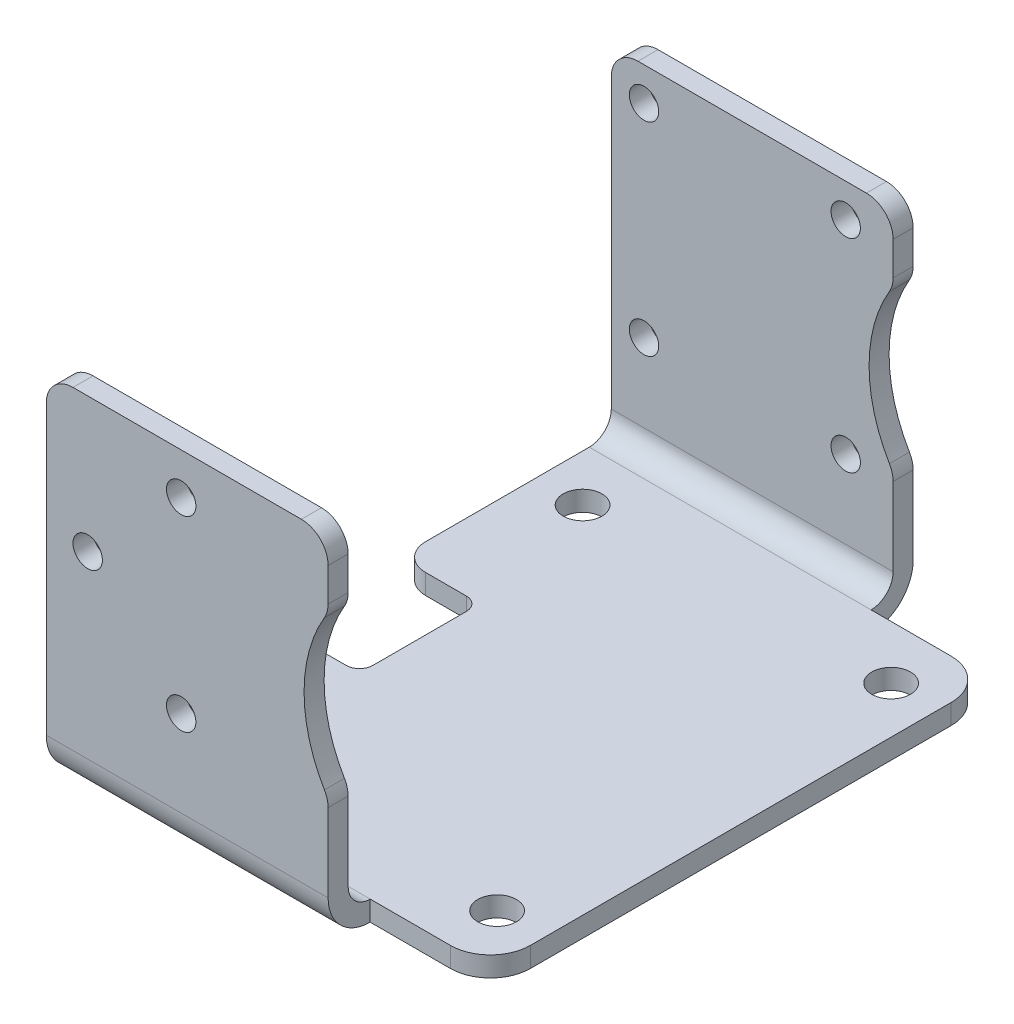
SolidWorks part; units mm, degrees
note: The reader was unsure of these and kept them because the rebuilt part matched: flange length of "Edge-Flange2".
material "1.0037 (S235JR)"
ref_plane "Front Plane" through (0, 0, 0) normal (0, 0, 1) x (1, 0, 0)
ref_plane "Top Plane" through (0, 0, 0) normal (0, 1, 0) x (1, 0, 0)
ref_plane "Right Plane" through (0, 0, 0) normal (1, 0, 0) x (0, 0, -1)
sketch "Sketch1" plane through (0, 0, 0) normal (0, 1, 0) x (1, 0, 0)
  line L1 (20.05, -20.4) -> (-20.05, -20.4)
  line L2 (20.05, -20.4) -> (20.05, 20.4)
  line L3 (20.05, 20.4) -> (-20.05, 20.4)
  line L4 (-20.05, -20.4) -> (-20.05, 20.4)
  line L5 (20.05, -20.4) -> (-20.05, 20.4) construction
  line L6 (20.05, 20.4) -> (-20.05, -20.4) construction
  point P0 (0, 0)
  dimension "D1" = 40.8
  dimension "D2" = 40.1
base flange "Base-Flange1" sketch "Sketch1" thickness 1.5 reverse thickness direction no parameters "D1"=1.65
edge flange "Edge-Flange2" sketch "Sketch21" flange profiles "Sketch21", "Sketch22" flange angle 90 flange length 25.2 flange position material outside bend radius 1.65 thickness 1.5 relief rectangular parameters "D1"=2, "D6"=10, "D8"=1
sketch "Sketch21" plane through (0, 0, 20.4) normal (0, 0, 1) x (1, 0, 0)
  line L0 (-20.05, 0) -> (20.05, 0) construction
  line L1 (-20.05, 0) -> (20.05, 0)
  line L2 (-20.05, 0) -> (-20.05, 25.2)
  line L3 (-20.05, 25.2) -> (20.05, 25.2)
  line L4 (20.05, 25.2) -> (20.05, 0)
sketch "Sketch22" plane through (0, 0, -20.4) normal (0, 0, -1) x (-1, 0, 0)
  line L0 (-20.05, 0) -> (20.05, 0) construction
  line L1 (-20.05, 0) -> (20.05, 0)
  line L2 (-20.05, 0) -> (-20.05, 25.2)
  line L3 (-20.05, 25.2) -> (20.05, 25.2)
  line L4 (20.05, 25.2) -> (20.05, 0)
bend "EdgeBend3" bend radius 1.65 bend angle 90 parameters "D5"=1
bend "EdgeBend4" bend radius 1.65 bend angle 90 parameters "D5"=2
sketch "Sketch23" plane through (20.05, 0, 0) normal (1, 0, 0) x (0, 0, -1)
  line L1 (-18.75, -1.5) -> (-21.9, -1.5)
  line L2 (-18.75, -1.5) -> (-18.75, 25.2)
  line L3 (-18.75, 25.2) -> (-21.9, 25.2)
  line L4 (-21.9, -1.5) -> (-21.9, 25.2)
  line L5 (18.75, -1.5) -> (21.9, -1.5)
  line L6 (18.75, -1.5) -> (18.75, 25.2)
  line L7 (18.75, 25.2) -> (21.9, 25.2)
  line L8 (21.9, -1.5) -> (21.9, 25.2)
extrude "Cut-Extrude3" cut sketch "Sketch23" against normal blind 19 normal cut yes
sketch "Sketch24" plane through (0, 0, -21.9) normal (0, 0, -1) x (-1, 0, 0)
  line L0 (-1.05, 0) -> (-20.05, 0) construction
  line L2 (20.05, 1.65) -> (20.05, 25.2) construction
  circle A0 centre (-10.25, 14.1) radius 11
  dimension "D1" = 14.1
  dimension "D2" = 22
  dimension "D3" = 30.3
extrude "Cut-Extrude4" cut sketch "Sketch24" against normal through all normal cut yes
sketch "Sketch26" plane through (0, 0, 0) normal (0, 1, 0) x (1, 0, 0)
  line L0 (20.05, -18.75) -> (1.05, -18.75) construction
  line L1 (20.05, 18.75) -> (10.05, 18.75)
  line L2 (20.05, 18.75) -> (20.05, -18.75)
  line L3 (20.05, -18.75) -> (10.05, -18.75)
  line L4 (10.05, 18.75) -> (10.05, -18.75)
  dimension "D1" = 10
extrude "Cut-Extrude5" cut sketch "Sketch26" against normal through all normal cut yes
sketch "Sketch27" plane through (0, 0, 0) normal (0, 1, 0) x (1, 0, 0)
  line L0 (6.55, 0) -> (10.05, 0) construction
  line L1 (-16.55, 14.75) -> (6.55, 14.75) construction
  line L2 (-16.55, 14.75) -> (-16.55, -14.75) construction
  line L3 (-16.55, -14.75) -> (6.55, -14.75) construction
  line L4 (6.55, 14.75) -> (6.55, -14.75) construction
  line L5 (10.05, 18.75) -> (10.05, -18.75) construction
  line L6 (-16.55, 0) -> (-20.05, 0) construction
  line L7 (-20.05, 18.75) -> (-20.05, -18.75) construction
  line L8 (1.05, 18.75) -> (10.05, 18.75) construction
  circle A0 centre (-16.55, 14.75) radius 1.45
  circle A1 centre (6.55, 14.75) radius 1.45
  circle A2 centre (6.55, -14.75) radius 1.45
  circle A3 centre (-16.55, -14.75) radius 1.45
  point P4 (6.55, 0)
  dimension "D1" = 2.9
  dimension "D2" = 4
  dimension "D3" = 3.5
extrude "Cut-Extrude6" cut sketch "Sketch27" against normal through all normal cut yes
fillet "Fillet1" radius 3 2 edges at (10.05, -0.75, -18.75) (10.05, -0.75, 18.75)
fillet "Fillet2" radius 2 8 edges at (1.05, 8.0701, 21.15) (1.05, 20.1299, 21.15) (1.05, 8.0701, -21.15) (1.05, 20.1299, -21.15) (1.05, 25.2, -21.15) (-20.05, 25.2, -21.15) (-20.05, 25.2, 21.15) (1.05, 25.2, 21.15)
hole_wizard "Ø2.0mm Dowel Hole1" positions "Sketch28" profile "Sketch29" hole size "Ø2.0" standard "ANSI Metric" end condition up to next
sketch "Sketch28" plane through (0, 0, -21.9) normal (0, 0, -1) x (-1, 0, 0)
  point P0 (2.5, 22.7)
  point P3 (17.6, 22.7)
  point P6 (2.5, 7.5)
  point P9 (17.6, 7.5)
sketch "Sketch29" plane through (-2.5, 22.7, -21.9) normal (1, 0, 0) x (0, 1, 0)
  line L0 (0, 0) -> (0, 1.5)
  line L1 (0, 1.5) -> (1.1, 1.5)
  line L2 (1.1, 1.5) -> (1.1, 0)
  line L5 (1.1, 0) -> (0, 0)
  line L11 (0, -6.35) -> (0, 107.95) construction
  dimension "Thru Hole Dia." = 2.2
  dimension "Thru Hole Depth" = 1.5
hole_wizard "Ø2.0mm Dowel Hole2" positions "Sketch30" profile "Sketch31" hole size "Ø2.0" standard "ANSI Metric" end condition up to next
sketch "Sketch30" plane through (0, 0, 21.9) normal (0, 0, 1) x (1, 0, 0)
  point P0 (-16.95, 15.1)
  point P3 (-9.95, 22.1)
  point P6 (-9.95, 8.1)
sketch "Sketch31" plane through (-16.95, 15.1, 21.9) normal (1, 0, 0) x (0, -1, 0)
  line L0 (0, 0) -> (0, 1.5)
  line L1 (0, 1.5) -> (1.1, 1.5)
  line L2 (1.1, 1.5) -> (1.1, 0)
  line L5 (1.1, 0) -> (0, 0)
  line L11 (0, -6.35) -> (0, 107.95) construction
  dimension "Thru Hole Dia." = 2.2
  dimension "Thru Hole Depth" = 1.5
sketch "Sketch32" plane through (0, -1.5, 0) normal (0, -1, 0) x (1, 0, 0)
  line L0 (-20.05, -18.75) -> (-20.05, 18.75) construction
  line L1 (-20.05, 4.5) -> (-20.05, -4.5)
  line L4 (-20, 3.5) -> (-20, -3.5)
  line L5 (-15, 4.5) -> (-19, 4.5)
  line L6 (-14, -3.5) -> (-14, 3.5)
  line L7 (-19, -4.5) -> (-15, -4.5)
  line L9 (-15, 4.5) -> (-20.05, 4.5)
  line L10 (-14, -3.5) -> (-14, 3.5)
  line L11 (-20.05, -4.5) -> (-15, -4.5)
  arc A4 (-19, 4.5) -> (-20, 3.5) centre (-19, 3.5) ccw
  arc A5 (-14, 3.5) -> (-15, 4.5) centre (-15, 3.5) ccw
  arc A6 (-15, -4.5) -> (-14, -3.5) centre (-15, -3.5) ccw
  arc A7 (-20, -3.5) -> (-19, -4.5) centre (-19, -3.5) ccw
  arc A9 (-14, 3.5) -> (-15, 4.5) centre (-15, 3.5) ccw
  arc A10 (-15, -4.5) -> (-14, -3.5) centre (-15, -3.5) ccw
  dimension "D1" = 0
extrude "Cut-Extrude7" cut sketch "Sketch32" against normal through all normal cut yes
fillet "Fillet3" radius 2 2 edges at (-20.05, -0.75, -4.5) (-20.05, -0.75, 4.5)
sketch "Bend-Lines1" [suppressed] plane through (0, 0, 0) normal (0, 1, 0) x (1, 0, 0)
sketch "Bounding-Box1" [suppressed] plane through (0, 0, 0) normal (0, 1, 0) x (1, 0, 0)
sheet metal parameters "Sheet-Metal1" thickness 1.5 parameters "D1"=1.5
flat pattern "Flat-Pattern1" [suppressed]
sketch "Bend-Lines2" plane through (0, 0, 0) normal (0, 1, 0) x (1, 0, 0)
sketch3d "Bounding-Box2" [suppressed]
  line L0 (-20.05, 20.3, 0) -> (-20.05, -20.3, 0) construction
  line L1 (20.05, 20.3, 0) -> (20.05, -20.3, 0) construction
  line L2 (-20.05, 20.3, 0) -> (20.05, 20.3, 0) construction
  line L3 (-20.05, -20.3, 0) -> (20.05, -20.3, 0) construction
sheet metal parameters "Sheet-Metal5" thickness 1.5 parameters "D1"=1.5
flat pattern "Flat-Pattern1"
sketch "Bend-Lines2" plane through (0, 0, 0) normal (0, 1, 0) x (1, 0, 0)
  line L0 (20.05, 20.4598) -> (-20.05, 20.4598) construction
  line L1 (-20.05, -20.4598) -> (20.05, -20.4598) construction
  line L2 (20.05, 20.4598) -> (-20.05, 20.4598) construction
  line L3 (-20.05, -20.4598) -> (20.05, -20.4598) construction
sketch3d "Bounding-Box2" [suppressed]
  line L0 (-20.05, 45.6197, 0) -> (-20.05, -45.6197, 0) construction
  line L1 (20.05, 45.6197, 0) -> (20.05, -45.6197, 0) construction
  line L2 (-20.05, 45.6197, 0) -> (20.05, 45.6197, 0) construction
  line L3 (-20.05, -45.6197, 0) -> (20.05, -45.6197, 0) construction
bend of the flat pattern "EdgeBend3>1"
bend of the flat pattern "EdgeBend4>1"
sheet metal parameters "Sheet-Metal6" thickness 1.5 parameters "D1"=1.5
flat pattern "Flat-Pattern1"
sketch "Bend-Lines2" plane through (0, 0, 0) normal (0, 1, 0) x (1, 0, 0)
  line L0 (1.05, 20.4598) -> (-20.05, 20.4598) construction
  line L1 (-20.05, -20.4598) -> (1.05, -20.4598) construction
  line L2 (1.05, 20.4598) -> (-20.05, 20.4598) construction
  line L3 (-20.05, -20.4598) -> (1.05, -20.4598) construction
sketch3d "Bounding-Box2" [suppressed]
  line L0 (-20.05, 45.6197, 0) -> (-20.05, -45.6197, 0) construction
  line L1 (20.05, 45.6197, 0) -> (20.05, -45.6197, 0) construction
  line L2 (-20.05, 45.6197, 0) -> (20.05, 45.6197, 0) construction
  line L3 (-20.05, -45.6197, 0) -> (20.05, -45.6197, 0) construction
bend of the flat pattern "EdgeBend3>1"
bend of the flat pattern "EdgeBend4>1"
sheet metal parameters "Sheet-Metal7" thickness 1.5 parameters "D1"=1.5
flat pattern "Flat-Pattern1"
sketch "Bend-Lines2" plane through (0, 0, 0) normal (0, 1, 0) x (1, 0, 0)
  line L0 (1.05, 20.4598) -> (-20.05, 20.4598) construction
  line L1 (-20.05, -20.4598) -> (1.05, -20.4598) construction
  line L2 (1.05, 20.4598) -> (-20.05, 20.4598) construction
  line L3 (-20.05, -20.4598) -> (1.05, -20.4598) construction
sketch3d "Bounding-Box2" [suppressed]
  line L0 (-20.05, 44.8197, 0) -> (-20.05, -44.8197, 0) construction
  line L1 (20.05, 44.8197, 0) -> (20.05, -44.8197, 0) construction
  line L2 (-20.05, 44.8197, 0) -> (20.05, 44.8197, 0) construction
  line L3 (-20.05, -44.8197, 0) -> (20.05, -44.8197, 0) construction
bend of the flat pattern "EdgeBend3>1"
bend of the flat pattern "EdgeBend4>1"
sheet metal parameters "Sheet-Metal8" thickness 1.5 parameters "D1"=1.5
flat pattern "Flat-Pattern1"
sketch "Bend-Lines2" plane through (0, 0, 0) normal (0, 1, 0) x (1, 0, 0)
  line L0 (1.05, 20.4598) -> (-20.05, 20.4598) construction
  line L1 (-20.05, -20.4598) -> (1.05, -20.4598) construction
  line L2 (1.05, 20.4598) -> (-20.05, 20.4598) construction
  line L3 (-20.05, -20.4598) -> (1.05, -20.4598) construction
sketch3d "Bounding-Box2" [suppressed]
  line L0 (-20.05, 45.8197, 0) -> (-20.05, -45.8197, 0) construction
  line L1 (10.05, 45.8197, 0) -> (10.05, -45.8197, 0) construction
  line L2 (-20.05, 45.8197, 0) -> (10.05, 45.8197, 0) construction
  line L3 (-20.05, -45.8197, 0) -> (10.05, -45.8197, 0) construction
bend of the flat pattern "EdgeBend3>1"
bend of the flat pattern "EdgeBend4>1"
sheet metal parameters "Sheet-Metal9" thickness 1.5 parameters "D1"=1.5
flat pattern "Flat-Pattern1"
sketch "Bend-Lines2" plane through (0, 0, 0) normal (0, 1, 0) x (1, 0, 0)
  line L0 (1.05, 20.4598) -> (-20.05, 20.4598) construction
  line L1 (-20.05, -20.4598) -> (1.05, -20.4598) construction
  line L2 (1.05, 20.4598) -> (-20.05, 20.4598) construction
  line L3 (-20.05, -20.4598) -> (1.05, -20.4598) construction
sketch3d "Bounding-Box2" [suppressed]
  line L0 (10.05, 45.8197, 0) -> (10.05, -45.8197, 0) construction
  line L1 (-20.05, 45.8197, 0) -> (-20.05, -45.8197, 0) construction
  line L2 (10.05, 45.8197, 0) -> (-20.05, 45.8197, 0) construction
  line L3 (10.05, -45.8197, 0) -> (-20.05, -45.8197, 0) construction
bend of the flat pattern "EdgeBend3>1"
bend of the flat pattern "EdgeBend4>1"
sheet metal parameters "Sheet-Metal10" thickness 1.5 parameters "D1"=1.5
flat pattern "Flat-Pattern1"
sketch "Bend-Lines2" plane through (0, 0, 0) normal (0, 1, 0) x (1, 0, 0)
  line L0 (1.05, 20.4598) -> (-20.05, 20.4598) construction
  line L1 (-20.05, -20.4598) -> (1.05, -20.4598) construction
  line L2 (1.05, 20.4598) -> (-20.05, 20.4598) construction
  line L3 (-20.05, -20.4598) -> (1.05, -20.4598) construction
sketch3d "Bounding-Box2" [suppressed]
  line L0 (10.05, 45.8197, 0) -> (10.05, -45.8197, 0) construction
  line L1 (-20.05, 45.8197, 0) -> (-20.05, -45.8197, 0) construction
  line L2 (10.05, 45.8197, 0) -> (-20.05, 45.8197, 0) construction
  line L3 (10.05, -45.8197, 0) -> (-20.05, -45.8197, 0) construction
bend of the flat pattern "EdgeBend3>1"
bend of the flat pattern "EdgeBend4>1"
sheet metal parameters "Sheet-Metal11" thickness 1.5 parameters "D1"=1.5
flat pattern "Flat-Pattern1"
sketch "Bend-Lines2" plane through (0, 0, 0) normal (0, 1, 0) x (1, 0, 0)
  line L0 (1.05, 20.535) -> (-20.05, 20.535) construction
  line L1 (-20.05, -20.535) -> (1.05, -20.535) construction
  line L2 (1.05, 20.535) -> (-20.05, 20.535) construction
  line L3 (-20.05, -20.535) -> (1.05, -20.535) construction
sketch3d "Bounding-Box2" [suppressed]
  line L0 (10.05, 45.9699, 0) -> (10.05, -45.9699, 0) construction
  line L1 (-20.05, 45.9699, 0) -> (-20.05, -45.9699, 0) construction
  line L2 (10.05, 45.9699, 0) -> (-20.05, 45.9699, 0) construction
  line L3 (10.05, -45.9699, 0) -> (-20.05, -45.9699, 0) construction
bend of the flat pattern "EdgeBend3>1"
bend of the flat pattern "EdgeBend4>1"
sheet metal parameters "Sheet-Metal12" thickness 1.5 parameters "D1"=1.5
flat pattern "Flat-Pattern1"
sketch "Bend-Lines2" plane through (0, 0, 0) normal (0, 1, 0) x (1, 0, 0)
  line L0 (1.05, 20.635) -> (-20.05, 20.635) construction
  line L1 (-20.05, -20.635) -> (1.05, -20.635) construction
  line L2 (1.05, 20.635) -> (-20.05, 20.635) construction
  line L3 (-20.05, -20.635) -> (1.05, -20.635) construction
sketch3d "Bounding-Box2" [suppressed]
  line L0 (10.05, 46.0699, 0) -> (10.05, -46.0699, 0) construction
  line L1 (-20.05, 46.0699, 0) -> (-20.05, -46.0699, 0) construction
  line L2 (10.05, 46.0699, 0) -> (-20.05, 46.0699, 0) construction
  line L3 (10.05, -46.0699, 0) -> (-20.05, -46.0699, 0) construction
bend of the flat pattern "EdgeBend3>1"
bend of the flat pattern "EdgeBend4>1"
